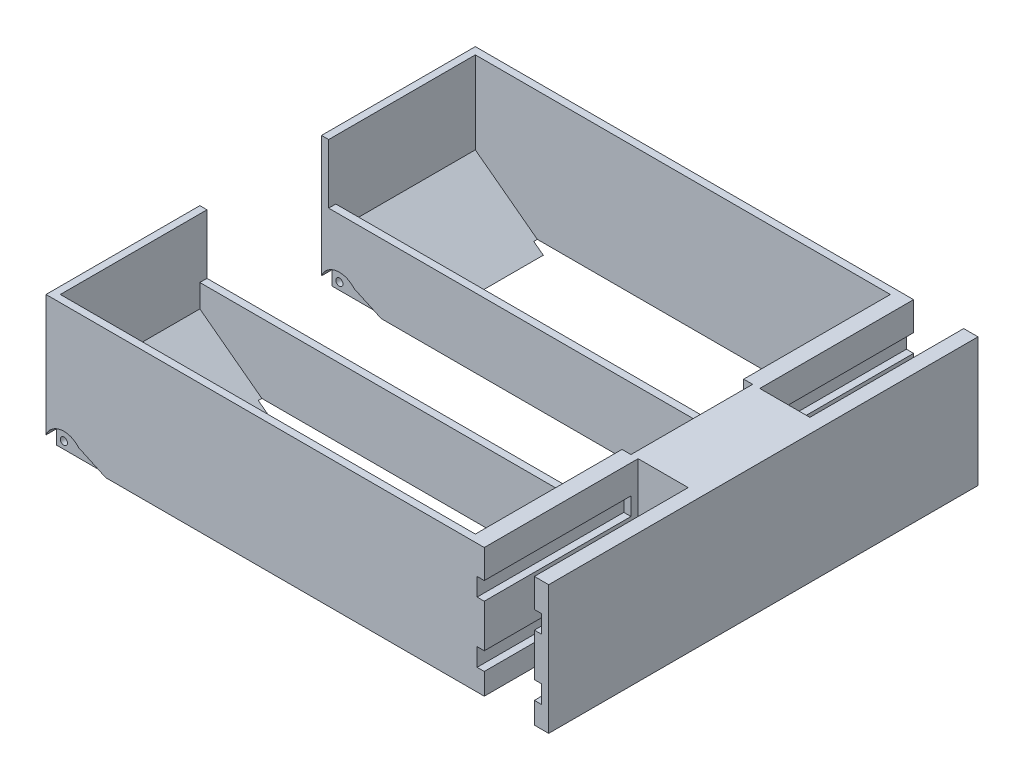
SolidWorks part; units mm, degrees
ref_plane "Front Plane" through (0, 0, 0) normal (0, 0, 1) x (1, 0, 0)
ref_plane "Top Plane" through (0, 0, 0) normal (0, 1, 0) x (1, 0, 0)
ref_plane "Right Plane" through (0, 0, 0) normal (1, 0, 0) x (0, 0, -1)
sketch "Sketch2" plane through (0, 0, 0) normal (0, 1, 0) x (1, 0, 0)
  line L1 (-60, -21.5) -> (60, -21.5)
  line L2 (-60, -21.5) -> (-60, 21.5)
  line L3 (-60, 21.5) -> (60, 21.5)
  line L4 (60, -21.5) -> (60, 21.5)
  line L5 (-60, -21.5) -> (60, 21.5) construction
  line L6 (-60, 21.5) -> (60, -21.5) construction
  point P0 (0, 0)
  dimension "D1" = 120
  dimension "D2" = 43
extrude "Boss-Extrude1" add sketch "Sketch2" along normal blind 38 contours L2 L3 L4 L1
sketch "Sketch3" plane through (0, 38, 0) normal (0, 1, 0) x (1, 0, 0)
  line L0 (-60, 21.5) -> (60, 21.5) construction
  line L1 (-58, -19.5) -> (58, -19.5)
  line L2 (-58, -19.5) -> (-58, 19.5)
  line L3 (-58, 19.5) -> (58, 19.5)
  line L4 (58, -19.5) -> (58, 19.5)
  line L5 (-58, -19.5) -> (58, 19.5) construction
  line L6 (-58, 19.5) -> (58, -19.5) construction
  line L7 (60, -21.5) -> (60, 21.5) construction
  point P0 (0, 0)
  dimension "D1" = 2
  dimension "D2" = 2
extrude "Cut-Extrude1" cut sketch "Sketch3" against normal up to vertex (38 mm away) up to point (-60, 0, -21.5)
sketch "Sketch4" plane through (0, 0, -19.5) normal (0, 0, 1) x (1, 0, 0)
  line L0 (-58, 0) -> (-58, 15)
  line L1 (-58, 15) -> (-38, 0)
  line L2 (-60, 0) -> (60, 0) construction
  line L3 (-38, 0) -> (-58, 0)
  dimension "D1" = 15
  dimension "D2" = 20
extrude "Boss-Extrude2" add sketch "Sketch4" along normal up to vertex (39 mm away) up to point (-58, 0, 19.5)
sketch "Sketch5" plane through (60, 0, 0) normal (1, 0, 0) x (0, 0, -1)
  line L1 (-21.5, 38) -> (21.5, 38)
  line L2 (-21.5, 38) -> (-21.5, 0)
  line L3 (-21.5, 0) -> (21.5, 0)
  line L4 (21.5, 38) -> (21.5, 0)
extrude "Boss-Extrude3" add sketch "Sketch5" along normal blind 2.5
sketch "Sketch6" plane through (0, 0, -21.5) normal (0, 0, -1) x (-1, 0, 0)
  line L0 (60, 0) -> (-62.5, 0) construction
  line L1 (-62.5, 38) -> (-60.5, 38)
  line L2 (-62.5, 38) -> (-62.5, 0)
  line L3 (-62.5, 0) -> (-60.5, 0)
  line L4 (-60.5, 38) -> (-60.5, 0)
  dimension "D1" = 2
extrude "Boss-Extrude4" add sketch "Sketch6" along normal blind 17 contours L4 L3 L2 L1
ref_plane "Plane1" through (0, 0, -38.5) normal (0, 0, -1) x (-1, 0, 0)
mirror "Mirror1" about plane through (0, 0, -38.5) normal (0, 0, -1) of bodies 105
sketch "Sketch7" plane through (62.5, 0, 0) normal (1, 0, 0) x (0, 0, -1)
  line L0 (38.5, 38) -> (38.5, 0) construction
  line L1 (98.5, 38) -> (-21.5, 38) construction
  line L2 (-21.5, 0) -> (98.5, 0) construction
  line L3 (-21.5, 19) -> (98.5, 19) construction
  line L4 (-21.5, 38) -> (-21.5, 0) construction
  line L5 (98.5, 38) -> (98.5, 0) construction
  line L11 (21.5, 0) -> (55.5, 0)
  line L12 (21.5, 0) -> (21.5, 38)
  line L13 (21.5, 38) -> (55.5, 38)
  line L14 (55.5, 0) -> (55.5, 38)
  line L15 (21.5, 0) -> (55.5, 38) construction
  line L16 (21.5, 38) -> (55.5, 0) construction
  point P12 (38.5, 19)
  point P13 (38.5, 19)
  dimension "D1" = 34
extrude "Boss-Extrude5" add sketch "Sketch7" along normal blind 18
sketch "Sketch8" plane through (0, 0, -21.5) normal (0, 0, 1) x (1, 0, 0)
  line L0 (80.5, 0) -> (62.5, 0) construction
  line L1 (80.5, 38) -> (76.5, 38)
  line L2 (80.5, 38) -> (80.5, 0)
  line L3 (80.5, 0) -> (76.5, 0)
  line L4 (76.5, 38) -> (76.5, 0)
  dimension "D1" = 4
extrude "Boss-Extrude6" add sketch "Sketch8" along normal up to vertex (43 mm away) up to point (62.5, 38, 21.5)
sketch "Sketch9" plane through (0, 0, 21.5) normal (0, 0, 1) x (1, 0, 0)
  line L0 (78.5, 38) -> (78.5, 0) construction
  line L1 (80.5, 38) -> (76.5, 38) construction
  line L2 (76.5, 0) -> (80.5, 0) construction
  line L3 (78.5, 19) -> (52.6863, 19) construction
  line L4 (78.5, 30) -> (60.5, 30)
  line L5 (78.5, 30) -> (78.5, 25)
  line L6 (78.5, 25) -> (60.5, 25)
  line L7 (60.5, 30) -> (60.5, 25)
  line L8 (78.5, 13) -> (60.5, 13)
  line L9 (60.5, 8) -> (60.5, 13)
  line L10 (78.5, 8) -> (60.5, 8)
  line L11 (78.5, 8) -> (78.5, 13)
  dimension "D1" = 18
  dimension "D2" = 5
  dimension "D3" = 25
extrude "Cut-Extrude2" cut sketch "Sketch9" against normal up to vertex (41 mm away) up to point (58, 38, -19.5)
mirror "Mirror2" about plane through (0, 0, -38.5) normal (0, 0, -1) of "Boss-Extrude6", "Cut-Extrude2"
sketch "Sketch11" plane through (80.5, 0, 0) normal (1, 0, 0) x (0, 0, -1)
  line L0 (98.5, 0) -> (98.5, 38) construction
  line L1 (-21.5, 0) -> (98.5, 0)
  line L2 (-21.5, 0) -> (-21.5, 2)
  line L3 (-21.5, 2) -> (98.5, 2)
  line L4 (98.5, 0) -> (98.5, 2)
  dimension "D1" = 2
extrude "Cut-Extrude3" cut sketch "Sketch11" against normal up to vertex (118.5 mm away) up to point (-38, 0, 19.5)
sketch "Sketch12" plane through (0, 0, 21.5) normal (0, 0, 1) x (1, 0, 0)
  line L0 (-60, 38) -> (-60, 0) construction
  line L1 (-38, 2) -> (-49.6148, 2)
  line L2 (-38, 2) -> (-38, 0)
  line L3 (-38, 0) -> (-60, 0)
  arc A0 (-49.6148, 2) -> (-60, 0) centre (-55, 2) ccw
  dimension "D1" = 5
extrude "Cut-Extrude4" cut sketch "Sketch12" against normal blind 3
ref_plane "Plane2" through (0, 0, 0) normal (0, 0, 1) x (1, 0, 0)
mirror "Mirror3" about plane through (0, 0, 0) normal (0, 0, 1) of "Cut-Extrude4"
mirror "Mirror4" about plane through (0, 0, -38.5) normal (0, 0, -1) of "Mirror3", "Cut-Extrude4"
sketch "Sketch13" plane through (0, 0, 18.5) normal (0, 0, 1) x (1, 0, 0)
  line L0 (-60, 0) -> (-38, 0) construction
  line L1 (-60, 0) -> (-60, 4) construction
  circle A0 centre (-58, 2) radius 1
  dimension "D1" = 2
  dimension "D2" = 2
  dimension "D3" = 2
extrude "Cut-Extrude5" cut sketch "Sketch13" against normal up to vertex (117 mm away) up to point (-60, 4, -98.5)
chamfer "Chamfer1" distance 10 angle 45 1 edges at (-49.6148, 2, 20)
chamfer "Chamfer2" distance 10 angle 45 1 edges at (-49.6148, 2, -20)
chamfer "Chamfer3" distance 10 angle 45 1 edges at (-49.6148, 2, -57)
chamfer "Chamfer4" distance 10 angle 45 1 edges at (-49.6148, 2, -97)
sketch "Sketch14" plane through (0, 38, 0) normal (0, 1, 0) x (1, 0, 0)
  line L0 (-60, 21.5) -> (60.5, 21.5) construction
  line L1 (-58, 19.5) -> (58, 19.5)
  line L2 (-58, 19.5) -> (-58, 21.5)
  line L3 (-58, 21.5) -> (58, 21.5)
  line L4 (58, 19.5) -> (58, 21.5)
  dimension "D1" = 116
extrude "Cut-Extrude6" cut sketch "Sketch14" against normal blind 16.6
mirror "Mirror5" about plane through (0, 0, -38.5) normal (0, 0, -1) of "Cut-Extrude6"
